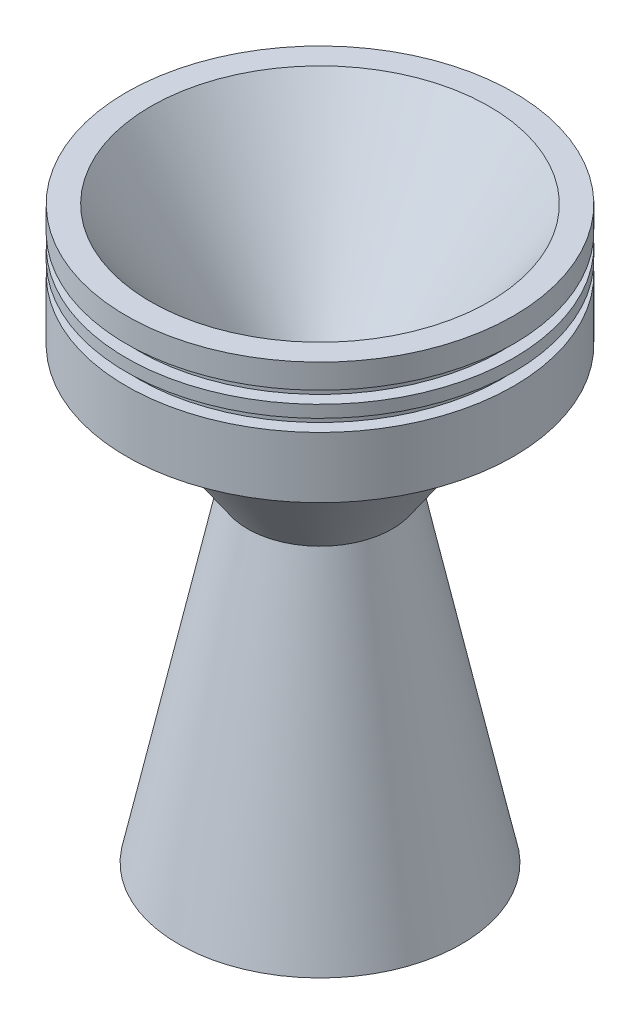
SolidWorks part; units mm, degrees
ref_plane "Front Plane" through (0, 0, 0) normal (0, 0, 1) x (1, 0, 0)
ref_plane "Top Plane" through (0, 0, 0) normal (0, 1, 0) x (1, 0, 0)
ref_plane "Right Plane" through (0, 0, 0) normal (1, 0, 0) x (0, 0, -1)
sketch "Sketch1" plane through (0, 0, 0) normal (0, 0, 1) x (1, 0, 0)
  line L0 (0, 0) -> (2.54, 0)
  line L8 (0, 0) -> (0, -2.54)
  line L9 (0, -2.54) -> (1.27, -2.54)
  line L10 (1.27, -2.54) -> (1.27, -3.81)
  line L11 (1.27, -3.81) -> (0, -3.81)
  line L12 (0, -3.81) -> (0, -5.08)
  line L13 (0, -5.08) -> (1.27, -5.08)
  line L14 (1.27, -5.08) -> (1.27, -6.35)
  line L15 (1.27, -6.35) -> (0, -6.35)
  line L16 (0, -6.35) -> (0, -12.7)
  line L18 (0, 0) -> (20.193, 0) construction
  line L19 (20.193, 0) -> (20.193, -59.4742) construction
  line L20 (2.54, 0) -> (16.002, -19.2257)
  line L22 (7.9868, -59.4742) -> (5.4468, -59.4742)
  line L23 (5.4468, -59.4742) -> (12.6522, -25.5757)
  line L24 (16.002, -19.2257) -> (16.002, -21.7657)
  line L25 (16.002, -21.7657) -> (7.9868, -59.4742)
  line L27 (20.193, -59.4742) -> (7.9868, -59.4742) construction
  line L29 (3.81, -12.7) -> (0, -12.7)
  line L30 (12.6522, -25.5757) -> (15.1922, -25.5757) construction
  line L31 (12.6522, -25.5757) -> (3.81, -12.7)
  point P13 (3.7816, -14.1257)
  dimension "D1" = 2.54
  dimension "D2" = 1.27
  dimension "D3" = 1.27
  dimension "D4" = 2.54
  dimension "D5" = 1.27
  dimension "D6" = 20.193
  dimension "D7" = 2.54
  dimension "D8" = 35
  dimension "D9" = 12
  dimension "D10" = 2.54
  dimension "D11" = 4.191
  dimension "D12" = 3.81
  dimension "D13" = 3.81
  dimension "D14" = 59.4742
  dimension "D15" = 6.35
revolve "base_revolve" add sketch "Sketch1" angle 360 about L19
